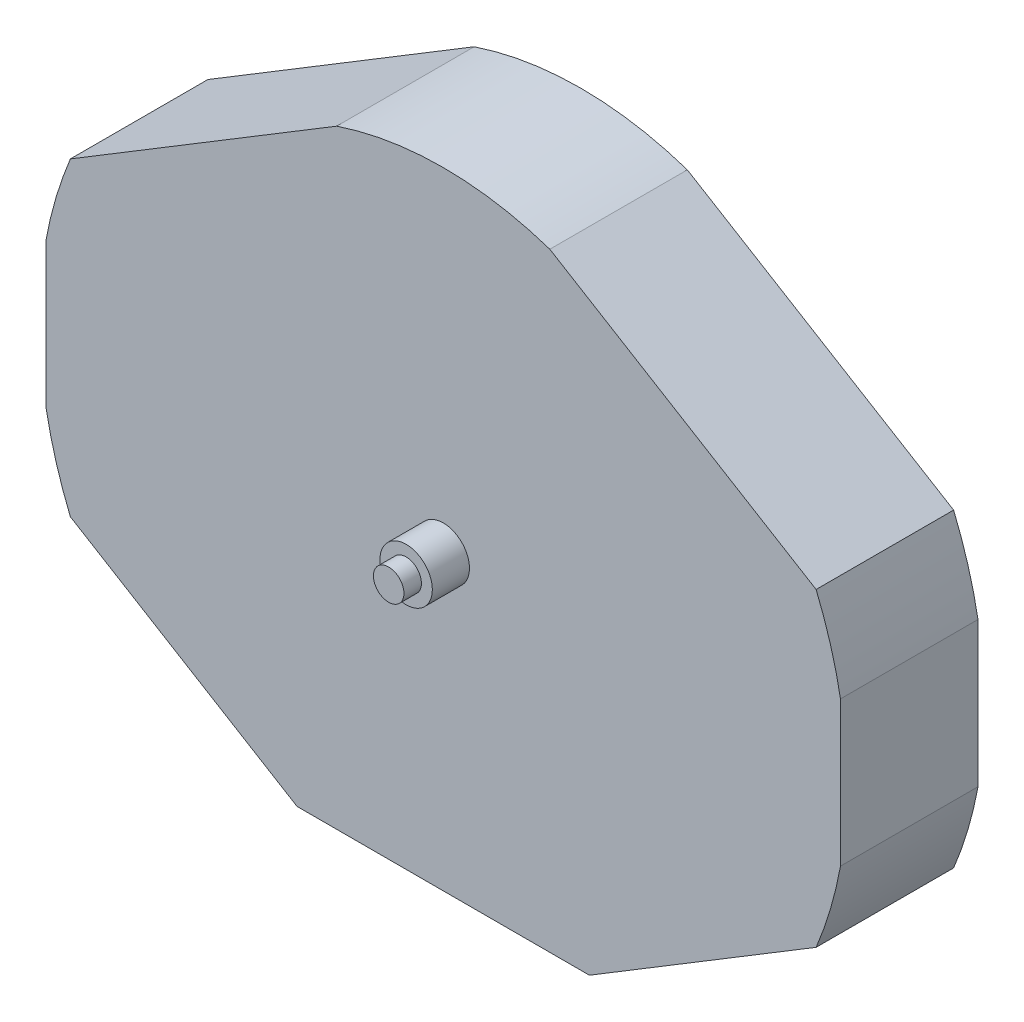
SolidWorks part; units mm, degrees
ref_plane "Plan de face" through (0, 0, 0) normal (0, 0, 1) x (1, 0, 0)
ref_plane "Plan de dessus" through (0, 0, 0) normal (0, 1, 0) x (1, 0, 0)
ref_plane "Plan de droite" through (0, 0, 0) normal (1, 0, 0) x (0, 0, -1)
sketch "Esquisse2" plane through (0, 0, 0) normal (0, 0, 1) x (1, 0, 0)
  line L0 (9.1, 1.6591) -> (9.1, -1.6591)
  line L1 (0, 0) -> (0, 7.65) construction
  line L2 (0, 0) -> (12.4009, 0) construction
  line L3 (2.4413, 7.25) -> (8.5417, 3.55)
  line L4 (-9.1, 1.6591) -> (-9.1, -1.6591)
  line L5 (-2.4413, 7.25) -> (-8.5417, 3.55)
  line L6 (-3.3481, -6.7) -> (3.3481, -6.7)
  line L8 (0, 0) -> (0, -6.7) construction
  line L10 (-3.3481, -6.7) -> (-8.5417, -3.55)
  line L11 (3.3481, -6.7) -> (8.5417, -3.55)
  arc A0 (2.4413, 7.25) -> (-2.4413, 7.25) centre (0, 0) ccw
  arc A1 (9.1, 1.6591) -> (8.5417, 3.55) centre (0, 0) ccw
  arc A2 (-9.1, 1.6591) -> (-8.5417, 3.55) centre (0, 0) cw
  arc A6 (-9.1, -1.6591) -> (-8.5417, -3.55) centre (0, 0) ccw
  arc A7 (9.1, -1.6591) -> (8.5417, -3.55) centre (0, 0) cw
  point P1 (-9.1, 0)
  point P6 (2.4413, 7.25)
  point P8 (8.5417, 3.55)
  point P11 (-2.4413, -7.25)
  point P14 (-8.5417, 3.55)
  point P15 (-2.4413, 7.25)
  point P17 (0, 0)
  point P22 (9.1, 0)
  point P23 (-8.5417, -3.55)
  point P24 (8.5417, -3.55)
  point P25 (2.4413, -7.25)
  dimension "D1" = 15.3
  dimension "D4" = 9.25
  dimension "D2" = 18.2
  dimension "D3" = 7.1
  dimension "D5" = 7.25
  dimension "D6" = 6.7
  dimension "D7" = 31.238
extrude "Boss.-Extru.1" add sketch "Esquisse2" along normal blind 3.15
sketch "Esquisse3" plane through (0, 0, 3.15) normal (0, 0, 1) x (1, 0, 0)
  line L0 (0, 7.65) -> (0, 0) construction
  line L1 (0, 0) -> (9.1, 0) construction
  line L2 (9.1, -1.6591) -> (9.1, 1.6591) construction
  arc A0 (2.4413, 7.25) -> (-2.4413, 7.25) centre (0, 0) ccw construction
  point P0 (-7.9, -3)
  point P1 (8.234, -1.9)
  point P13 (-3.4461, -2.4022)
  dimension "D1" = 1.9
  dimension "D2" = 8.234
  dimension "D3" = 3
  dimension "D4" = 7.9
ref_axis "DH1" through (-7.9, -3, 3.15) along (0, 0, 1)
ref_axis "DH2" through (8.234, -1.9, 3.15) along (0, 0, 1)
sketch "Esquisse4" plane through (0, 0, 3.15) normal (0, 0, 1) x (1, 0, 0)
  circle A0 centre (0, 0) radius 0.6
  dimension "D1" = 1.2
extrude "Boss.-Extru.2" add sketch "Esquisse4" along normal blind 0.85
sketch "Esquisse5" plane through (0, 0, 4) normal (0, 0, 1) x (1, 0, 0)
  circle A0 centre (0, 0) radius 0.35
  dimension "D1" = 0.7
extrude "Boss.-Extru.3" add sketch "Esquisse5" along normal blind 0.4
